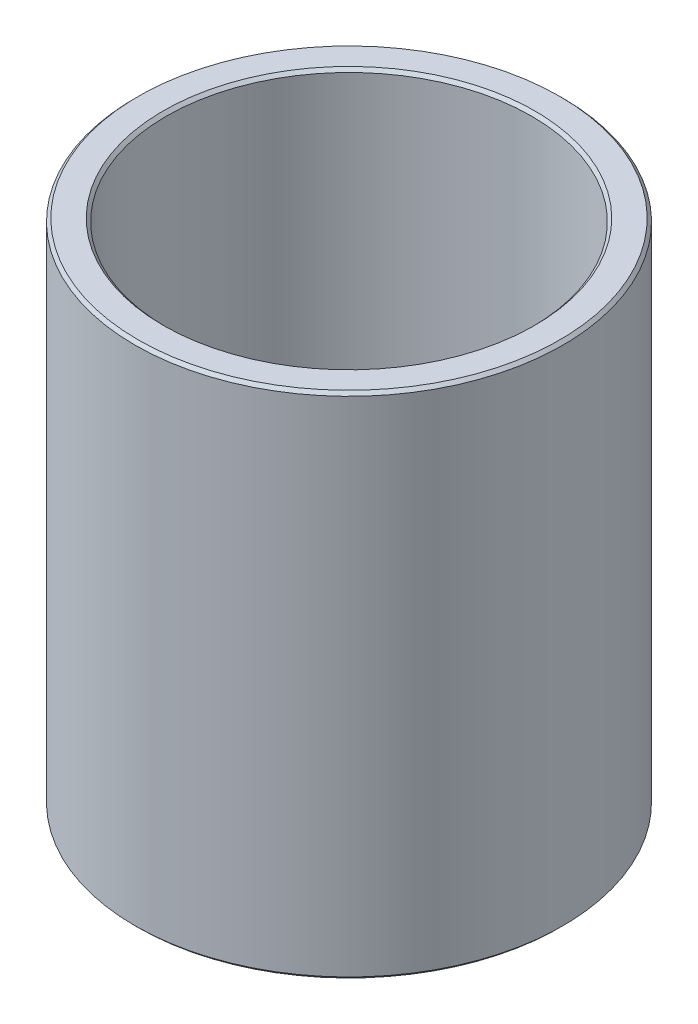
SolidWorks part; units mm, degrees
ref_plane "Front Plane" through (0, 0, 0) normal (0, 0, 1) x (1, 0, 0)
ref_plane "Top Plane" through (0, 0, 0) normal (0, 1, 0) x (1, 0, 0)
ref_plane "Right Plane" through (0, 0, 0) normal (1, 0, 0) x (0, 0, -1)
sketch "Sketch1" plane through (0, 0, 0) normal (0, 1, 0) x (1, 0, 0)
  circle A0 centre (0, 0) radius 40
  dimension "SLEEVE_OD" = 80
extrude "Boss-Extrude1" add sketch "Sketch1" along normal blind 95.1754
sketch "Sketch2" plane through (0, 0, 0) normal (0, 1, 0) x (1, 0, 0)
  circle A0 centre (0, 0) radius 34.169
  dimension "BORE_D" = 68.338
extrude "Cut-Extrude1" cut sketch "Sketch2" along normal through all
chamfer "Chamfer1" distance 0.5742 angle 45 4 edges at (0, 95.1754, 34.169) (0, 0, 34.169) (0, 0, 40) (0, 95.1754, 40)
